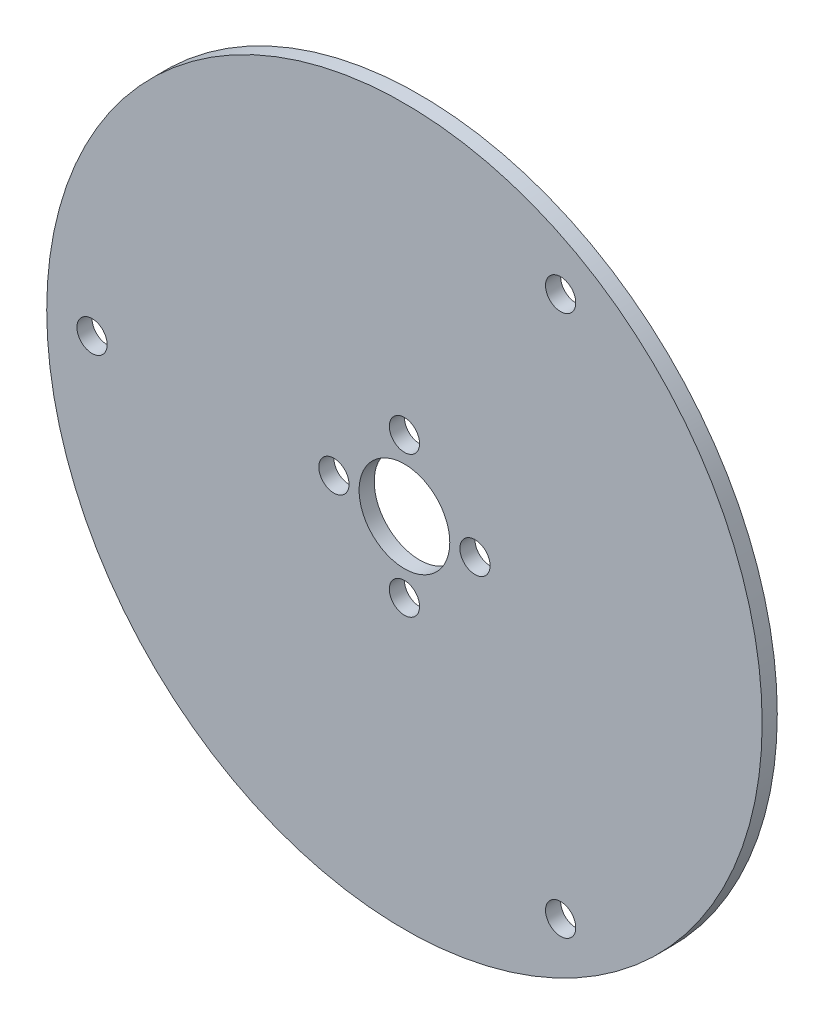
SolidWorks part; units mm, degrees
ref_plane "前视基准面" through (0, 0, 0) normal (0, 0, 1) x (1, 0, 0)
ref_plane "上视基准面" through (0, 0, 0) normal (0, 1, 0) x (1, 0, 0)
ref_plane "右视基准面" through (0, 0, 0) normal (1, 0, 0) x (0, 0, -1)
sketch "草图1" plane through (0, 0, 0) normal (0, 0, 1) x (1, 0, 0)
  circle A0 centre (0, 0) radius 35.5
extrude "凸台-拉伸1" add sketch "草图1" along normal blind 1.5
sketch "草图2" plane through (0, 0, 1.5) normal (0, 0, 1) x (1, 0, 0)
  circle A0 centre (0, 0) radius 4.5
extrude "切除-拉伸1" cut sketch "草图2" against normal blind 2
sketch "草图3" plane through (0, 0, 1.5) normal (0, 0, 1) x (1, 0, 0)
  circle A0 centre (0, 7) radius 1.5
  circle A1 centre (7, 0) radius 1.5
  circle A2 centre (0, -7) radius 1.5
  circle A3 centre (-7, 0) radius 1.5
  point P12 (0, 0)
  dimension "D1" = 4
extrude "切除-拉伸2" cut sketch "草图3" against normal blind 2
sketch "草图5" plane through (0, 0, 1.5) normal (0, 0, 1) x (1, 0, 0)
  circle A0 centre (-31, 0) radius 1.5
  circle A1 centre (15.5, 26.8468) radius 1.5
  circle A2 centre (15.5, -26.8468) radius 1.5
  point P10 (0, 0)
  dimension "D1" = 3
extrude "切除-拉伸3" cut sketch "草图5" against normal blind 2
